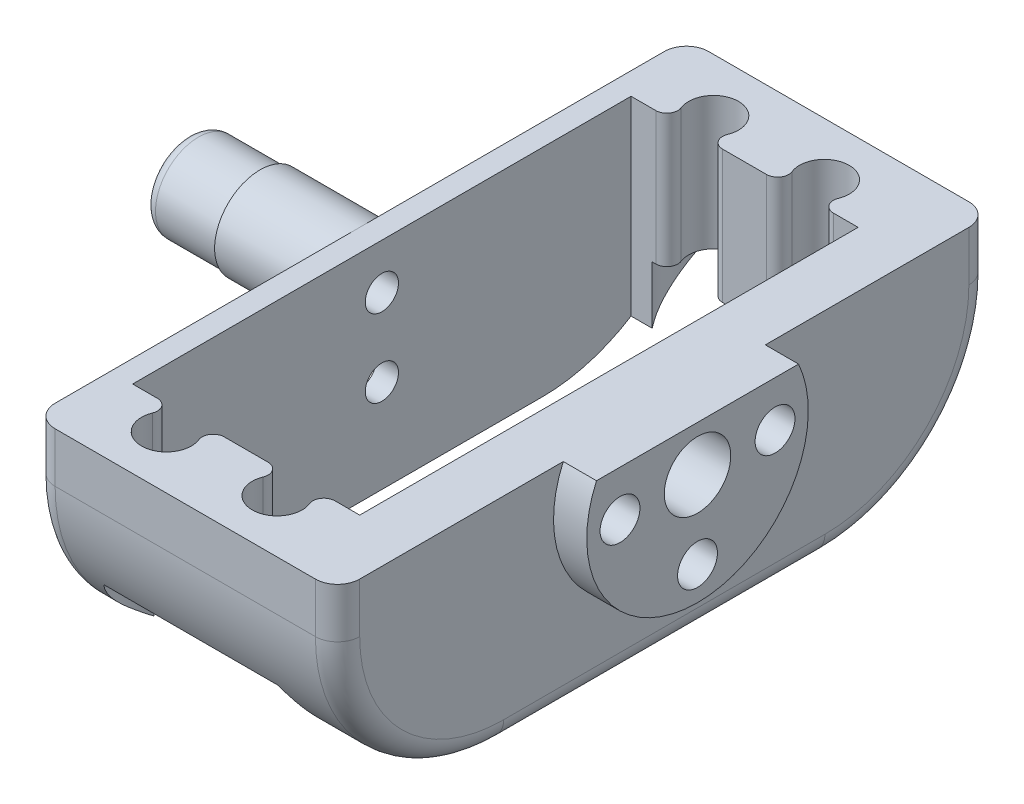
SolidWorks part; units mm, degrees
ref_plane "Front" through (0, 0, 0) normal (0, 0, 1) x (1, 0, 0)
ref_plane "Top" through (0, 0, 0) normal (0, 1, 0) x (1, 0, 0)
ref_plane "Right" through (0, 0, 0) normal (1, 0, 0) x (0, 0, -1)
sketch "Sketch1" plane through (0, 0, 0) normal (0, 1, 0) x (1, 0, 0)
  line L0 (15.25, 29.5) -> (-12.25, 29.5)
  line L1 (-10.25, -22.5) -> (10.25, -22.5)
  line L2 (-10.25, -22.5) -> (-10.25, 22.5)
  line L3 (-10.25, 22.5) -> (10.25, 22.5)
  line L4 (10.25, -22.5) -> (10.25, 22.5)
  line L5 (-10.25, -22.5) -> (10.25, 22.5) construction
  line L6 (-10.25, 22.5) -> (10.25, -22.5) construction
  line L7 (-12.25, 29.5) -> (-12.25, -29.5)
  line L8 (-12.25, -29.5) -> (15.25, -29.5)
  line L9 (15.25, -29.5) -> (15.25, 29.5)
  point P0 (0, 0)
  point P5 (15.25, 29.5)
  point P8 (-12.25, 29.5)
  point P13 (-12.25, 0)
  dimension "D1" = 45
  dimension "D2" = 20.5
  dimension "D3" = 7
  dimension "D4" = 5
  dimension "D5" = 2
extrude "Boss-Extrude1" add sketch "Sketch1" along normal blind 19.5
sketch "Sketch2" plane through (0, 19.5, 0) normal (0, 1, 0) x (1, 0, 0)
  line L7 (-5, -24.7) -> (5, -24.7) construction
  line L10 (-5, -24.7) -> (-5, 24.7) construction
  line L12 (-5, 24.7) -> (5, 24.7) construction
  line L13 (5, -24.7) -> (5, 24.7) construction
  line L14 (-5, -24.7) -> (5, 24.7) construction
  line L15 (-5, 24.7) -> (5, -24.7) construction
  circle A0 centre (-5, 24.7) radius 2.25
  circle A1 centre (5, 24.7) radius 2.25
  circle A2 centre (5, -24.7) radius 2.25
  circle A3 centre (-5, -24.7) radius 2.25
  point P0 (0, 0)
  point P3 (0, 0)
  dimension "D3" = 2.25
  dimension "D1" = 10
  dimension "D2" = 49.4
extrude "Cut-Extrude1" cut sketch "Sketch2" against normal through all both and the other way through all
fillet "Fillet1" radius 1 8 edges at (4.5283, 9.75, 22.5) (5.4717, 9.75, 22.5) (-4.5283, 9.75, 22.5) (-5.4717, 9.75, 22.5) (4.5283, 9.75, -22.5) (-5.4717, 9.75, -22.5) (-4.5283, 9.75, -22.5) (5.4717, 9.75, -22.5)
sketch "Sketch4" plane through (-12.25, 0, 0) normal (-1, 0, 0) x (0, 0, 1)
  line L0 (-29.5, 19.5) -> (29.5, 19.5) construction
  circle A0 centre (0, 15.4) radius 4.1
  point P7 (0, 0)
  dimension "D1" = 8.2
extrude "Boss-Extrude2" add sketch "Sketch4" along normal up to surface (15.5623 mm away)
sketch "Sketch5" plane through (15.25, 0, 0) normal (1, 0, 0) x (0, 0, -1)
  line L0 (0, 15.4) -> (0, 22.4) construction
  line L1 (0, 15.4) -> (7, 15.4) construction
  line L2 (0, 15.4) -> (0, 8.4) construction
  line L3 (0, 15.4) -> (-7, 15.4) construction
  circle A0 centre (0, 15.4) radius 3
  circle A2 centre (0, 15.4) radius 4.1 construction
  point P11 (0, 15.4)
  dimension "D1" = 6
  dimension "D2" = 7
  dimension "D3" = 4
hole_wizard "CBORE for M3 SHCS1" positions "Sketch8" profile "Sketch9" counterbore size "M3" standard "ANSI Metric" end condition up to next
sketch "Sketch8" plane through (10.25, 0, 0) normal (-1, 0, 0) x (0, 0, 1)
  point P0 (-7, 15.4)
  point P6 (7, 15.4)
  point P9 (0, 8.4)
  point P12 (0, 0)
sketch "Sketch9" plane through (10.25, 15.4, -7) normal (0, 1, 0) x (0, 0, 1)
  line L0 (0, 0) -> (0, 5)
  line L1 (0, 5) -> (1.8, 5)
  line L3 (1.8, 5) -> (1.8, 3)
  line L4 (1.8, 3) -> (3.25, 3)
  line L5 (3.25, 3) -> (3.25, 0)
  line L7 (3.25, 0) -> (0, 0)
  line L11 (0, -6.35) -> (0, 107.95) construction
  dimension "Thru Hole Dia." = 3.6
  dimension "Thru Hole Depth" = 5
  dimension "C'Bore Dia." = 6.5
  dimension "C'Bore Depth" = 3
extrude "Cut-Extrude3" cut sketch "Sketch5" against normal up to next contours A0
sketch "Sketch18" plane through (-27.8123, 0, 0) normal (-1, 0, 0) x (0, 0, 1)
  circle A0 centre (0, 15.4) radius 3.875
  circle A1 centre (0, 15.4) radius 4.1 construction
  circle A2 centre (0, 15.4) radius 4.1
  dimension "D1" = 7.75
extrude "Cut-Extrude11" cut sketch "Sketch18" against normal offset from surface (6.5623 mm away) 9 up to face at (-12.25, 12.3167, 0.6833)
sketch "Sketch20" plane through (-27.8123, 0, 0) normal (-1, 0, 0) x (0, 0, 1)
  circle A0 centre (0, 15.4) radius 1.5
  dimension "D1" = 3
extrude "Cut-Extrude12" cut sketch "Sketch20" against normal through all both and the other way through all
fillet "Fillet10" radius 1 1 edges at (-27.8123, 11.525, 0)
sketch "Sketch21" plane through (0, 0, -29.5) normal (0, 0, -1) x (-1, 0, 0)
  line L6 (5, -7.5) -> (-5, -7.5)
  line L8 (5, -7.5) -> (5, 7.5)
  line L9 (5, 7.5) -> (-5, 7.5)
  line L10 (-5, -7.5) -> (-5, 7.5)
  point P4 (0, -7.5)
  point P5 (-5, 0)
  dimension "D1" = 10
  dimension "D2" = 15
extrude "Cut-Extrude13" cut sketch "Sketch21" against normal through all both and the other way through all
fillet "Fillet8" radius 15 4 edges at (-8.625, 0, 29.5) (10.125, 0, 29.5) (-8.625, 0, -29.5) (10.125, 0, -29.5)
sketch "Sketch3" plane through (0, 19.5, 0) normal (0, 1, 0) x (1, 0, 0)
  line L11 (-1, -22.3906) -> (-1, -29.5) construction
  line L12 (-5, -29.3188) -> (-1, -27.0094) construction
  line L15 (-1, -27.0094) -> (-1, -22.3906) construction
  line L16 (-1, -22.3906) -> (-5, -20.0812) construction
  line L19 (0, 0) -> (-50000, 0) construction
  line L20 (-5, -20.0812) -> (-9, -22.3906) construction
  line L21 (-9, -22.3906) -> (-9, -27.0094) construction
  line L22 (-9, -27.0094) -> (-5, -29.3188) construction
  line L23 (-12.25, -29.5) -> (15.25, -29.5) construction
  line L24 (-1, -29.5) -> (-9, -29.5) construction
  line L25 (-9, -29.5) -> (-9, -22.3906) construction
  line L26 (9, -22.3906) -> (9, -29.5) construction
  line L27 (9, -22.3906) -> (5, -20.0812) construction
  line L38 (5, -20.0812) -> (1, -22.3906) construction
  line L39 (9, -29.5) -> (1, -29.5) construction
  line L40 (1, -29.5) -> (1, -22.3906) construction
  line L41 (5, -29.3188) -> (9, -27.0094) construction
  line L42 (9, -27.0094) -> (9, -22.3906) construction
  line L43 (1, -22.3906) -> (1, -27.0094) construction
  line L44 (1, -27.0094) -> (5, -29.3188) construction
  line L71 (1, 27.0094) -> (5, 29.3188) construction
  line L72 (1, 22.3906) -> (1, 27.0094) construction
  line L73 (9, 27.0094) -> (9, 22.3906) construction
  line L74 (5, 29.3188) -> (9, 27.0094) construction
  line L75 (-9, 27.0094) -> (-5, 29.3188) construction
  line L76 (-9, 22.3906) -> (-9, 27.0094) construction
  line L77 (-1, 27.0094) -> (-1, 22.3906) construction
  line L78 (-5, 29.3188) -> (-1, 27.0094) construction
  line L89 (1, 29.5) -> (1, 22.3906) construction
  line L90 (9, 29.5) -> (1, 29.5) construction
  line L91 (5, 20.0812) -> (1, 22.3906) construction
  line L92 (9, 22.3906) -> (5, 20.0812) construction
  line L93 (9, 22.3906) -> (9, 29.5) construction
  line L94 (-9, 29.5) -> (-9, 22.3906) construction
  line L95 (-1, 29.5) -> (-9, 29.5) construction
  line L96 (-5, 20.0812) -> (-9, 22.3906) construction
  line L97 (-1, 22.3906) -> (-5, 20.0812) construction
  line L98 (-1, 22.3906) -> (-1, 29.5) construction
  line L99 (19, -22.3906) -> (19, -29.5) [skipped]
  line L100 (19, -22.3906) -> (15, -20.0812) [skipped]
  line L101 (15, -20.0812) -> (11, -22.3906) [skipped]
  line L102 (19, -29.5) -> (11, -29.5) [skipped]
  line L103 (11, -29.5) -> (11, -22.3906) [skipped]
  line L104 (29, -22.3906) -> (29, -29.5) [skipped]
  line L105 (29, -22.3906) -> (25, -20.0812) [skipped]
  line L106 (25, -20.0812) -> (21, -22.3906) [skipped]
  line L107 (29, -29.5) -> (21, -29.5) [skipped]
  line L108 (21, -29.5) -> (21, -22.3906) [skipped]
  line L109 (15, -29.3188) -> (19, -27.0094) construction
  line L110 (19, -27.0094) -> (19, -22.3906) construction
  line L111 (11, -22.3906) -> (11, -27.0094) construction
  line L112 (11, -27.0094) -> (15, -29.3188) construction
  line L113 (25, -29.3188) -> (29, -27.0094) construction
  line L114 (29, -27.0094) -> (29, -22.3906) construction
  line L115 (21, -22.3906) -> (21, -27.0094) construction
  line L116 (21, -27.0094) -> (25, -29.3188) construction
  circle A0 centre (-5, -24.7) radius 4
  circle A1 centre (5, -24.7) radius 2.25 construction
  circle A2 centre (5, -24.7) radius 4
  circle A4 centre (-5, -24.7) radius 2.25 construction
  circle A8 centre (5, 24.7) radius 4
  circle A9 centre (-5, 24.7) radius 4
  circle A10 centre (15, -24.7) radius 4 construction
  circle A11 centre (25, -24.7) radius 4 construction
  dimension "D1" = 8
  dimension "D2" = 4
extrude "Cut-Extrude2" cut sketch "Sketch3" against normal through all from offset 12 offset against normal yes
fillet "Fillet11" radius 2 10 edges at (-12.25, 17.25, -29.5) (-12.25, 17.25, 29.5) (-12.25, 4.3934, 25.1066) (-12.25, 0, 0) (15.25, 17.25, 29.5) (15.25, 4.3934, 25.1066) (15.25, 0, 0) (15.25, 17.25, -29.5) (-12.25, 4.3934, -25.1066) (15.25, 4.3934, -25.1066)
sketch "Sketch22" plane through (15.25, 0, 0) normal (1, 0, 0) x (0, 0, -1)
  line L0 (9.1209, 19.5) -> (-9.1209, 19.5)
  line L1 (-27.5, 19.5) -> (27.5, 19.5) construction
  circle A0 centre (0, 15.4) radius 10 construction
  circle A1 centre (7, 15.4) radius 1.8 construction
  circle A2 centre (0, 8.4) radius 1.8 construction
  circle A3 centre (0, 15.4) radius 3 construction
  circle A4 centre (-7, 15.4) radius 1.8 construction
  circle A5 centre (7, 15.4) radius 1.8
  circle A6 centre (0, 8.4) radius 1.8
  circle A7 centre (0, 15.4) radius 3
  circle A8 centre (-7, 15.4) radius 1.8
  arc A9 (-9.1209, 19.5) -> (9.1209, 19.5) centre (0, 15.4) ccw
  dimension "D1" = 20
extrude "Boss-Extrude3" add sketch "Sketch22" along normal blind 3
sketch "Sketch23" plane through (10.25, 0, 0) normal (-1, 0, 0) x (0, 0, 1)
  circle A0 centre (0, 8.4) radius 1.8 construction
  circle A1 centre (0, 8.4) radius 1.8 construction
  circle A2 centre (0, 8.4) radius 1.5
  circle A3 centre (0, 15.4) radius 1.5 construction
extrude "Cut-Extrude14" cut sketch "Sketch23" along normal through all
